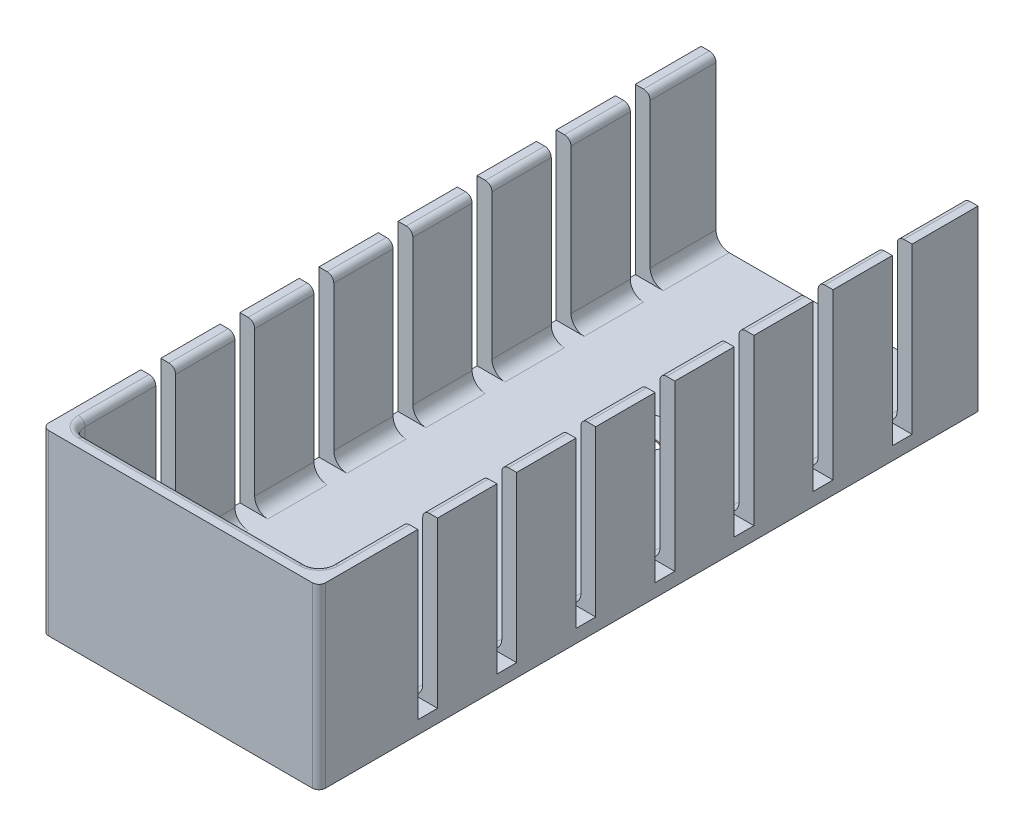
SolidWorks part; units mm, degrees
ref_plane "Front Plane" through (0, 0, 0) normal (0, 0, 1) x (1, 0, 0)
ref_plane "Top Plane" through (0, 0, 0) normal (0, 1, 0) x (1, 0, 0)
ref_plane "Right Plane" through (0, 0, 0) normal (1, 0, 0) x (0, 0, -1)
sketch "Sketch1" plane through (0, 0, 0) normal (0, 1, 0) x (1, 0, 0)
  line L1 (-21, -50) -> (21, -50)
  line L2 (-21, -50) -> (-21, 50)
  line L3 (-21, 50) -> (21, 50)
  line L4 (21, -50) -> (21, 50)
  line L5 (-21, -50) -> (21, 50) construction
  line L6 (-21, 50) -> (21, -50) construction
  point P0 (0, 0)
  dimension "D1" = 42
  dimension "D2" = 100
extrude "Boss-Extrude1" add sketch "Sketch1" along normal blind 2
sketch "Sketch2" plane through (0, 2, 0) normal (0, 1, 0) x (1, 0, 0)
  line L0 (-21, 50) -> (-18.75, 50)
  line L1 (21, 50) -> (-21, 50) construction
  line L2 (-18.75, 50) -> (-18.75, -47.75)
  line L3 (-18.75, -47.75) -> (18.75, -47.75)
  line L4 (21, -50) -> (21, 50)
  line L5 (21, 50) -> (-21, 50)
  line L6 (-21, 50) -> (-21, -50)
  line L7 (-21, -50) -> (21, -50)
  line L8 (21, -50) -> (21, 50)
  line L10 (-21, 50) -> (-21, -50)
  line L11 (-21, -50) -> (21, -50)
  line L12 (18.75, -47.75) -> (18.75, 50)
  line L13 (18.75, 50) -> (21, 50)
  line L14 (0, -47.75) -> (0, 0) construction
  line L15 (0, -47.75) -> (0, -50) construction
  dimension "D2" = 37.5
  dimension "D1" = 0
extrude "Boss-Extrude2" add sketch "Sketch2" along normal blind 25
fillet "Fillet1" radius 2 5 edges at (18.75, 2, -1.125) (0, 2, 47.75) (-18.75, 2, -1.125) (18.75, 14.5, 47.75) (-18.75, 14.5, 47.75)
sketch "Sketch3" plane through (0, 27, 0) normal (0, 1, 0) x (1, 0, 0)
  line L0 (-21, 50) -> (-21, -50) construction
  line L1 (-21, 40) -> (21, 40)
  line L2 (-21, 40) -> (-21, 37)
  line L3 (-21, 37) -> (21, 37)
  line L4 (21, 40) -> (21, 37)
  line L5 (21, -50) -> (21, 50) construction
  line L6 (21, 50) -> (18.75, 50) construction
  dimension "D1" = 10
  dimension "D2" = 3
extrude "Cut-Extrude1" cut sketch "Sketch3" against normal up to surface (25 mm away) up to face at (0, 2, -2.125)
pattern_linear "LPattern1" count 7 spacing 12 along (0, 0, 1) of "Cut-Extrude1"
sketch "Sketch4" plane through (0, 2, 0) normal (0, 1, 0) x (1, 0, 0)
  circle A0 centre (0.5607, 20) radius 1.4 construction
  circle A1 centre (0.5607, 20) radius 1.4 construction
  circle A2 centre (0.5607, -20) radius 1.4 construction
  circle A3 centre (0.5607, -20) radius 1.4 construction
hole_wizard "CSK for M3 Flat Head Machine Screw1" positions "3DSketch1" profile "Sketch5" countersink size "M3" standard "ANSI Metric" end condition through all
sketch3d "3DSketch1"
  point P0 (0.5607, 2, -20)
  point P3 (0.5607, 2, 20)
sketch "Sketch5" plane through (0.5607, 2, -20) normal (1, 0, 0) x (0, 0, 1)
  line L0 (0, 0) -> (0, 2)
  line L1 (0, 2) -> (1.6, 2)
  line L2 (1.6, 2) -> (1.6, 1.775)
  line L3 (1.6, 1.775) -> (3.375, 0)
  line L5 (3.375, 0) -> (0, 0)
  line L6 (-1.6, 1.775) -> (-3.375, 0) construction
  line L11 (0, -6.35) -> (0, 107.95) construction
  dimension "Thru Hole Dia." = 3.2
  dimension "Thru Hole Depth" = 2
  dimension "Near C'Sink Dia." = 6.75
  dimension "Near C'Sink Angle" = 90
fillet "Fillet2" radius 1 21 edges at (18.75, 27, 40.375) (18.1642, 27, 47.1642) (-18.75, 27, 40.375) (-18.1642, 27, 47.1642) (0, 27, 47.75) (18.75, 27, -45) (18.75, 27, -32.5) (18.75, 27, -20.5) (18.75, 27, -8.5) (18.75, 27, 3.5) (-18.75, 27, 3.5) (-18.75, 27, -8.5) (-18.75, 27, -20.5) (-18.75, 27, -32.5) (-18.75, 27, -45) (18.75, 27, 27.5) (18.75, 27, 15.5) (-18.75, 27, 15.5) (-18.75, 27, 27.5) (21, 13.5, 50) (-21, 13.5, 50)
